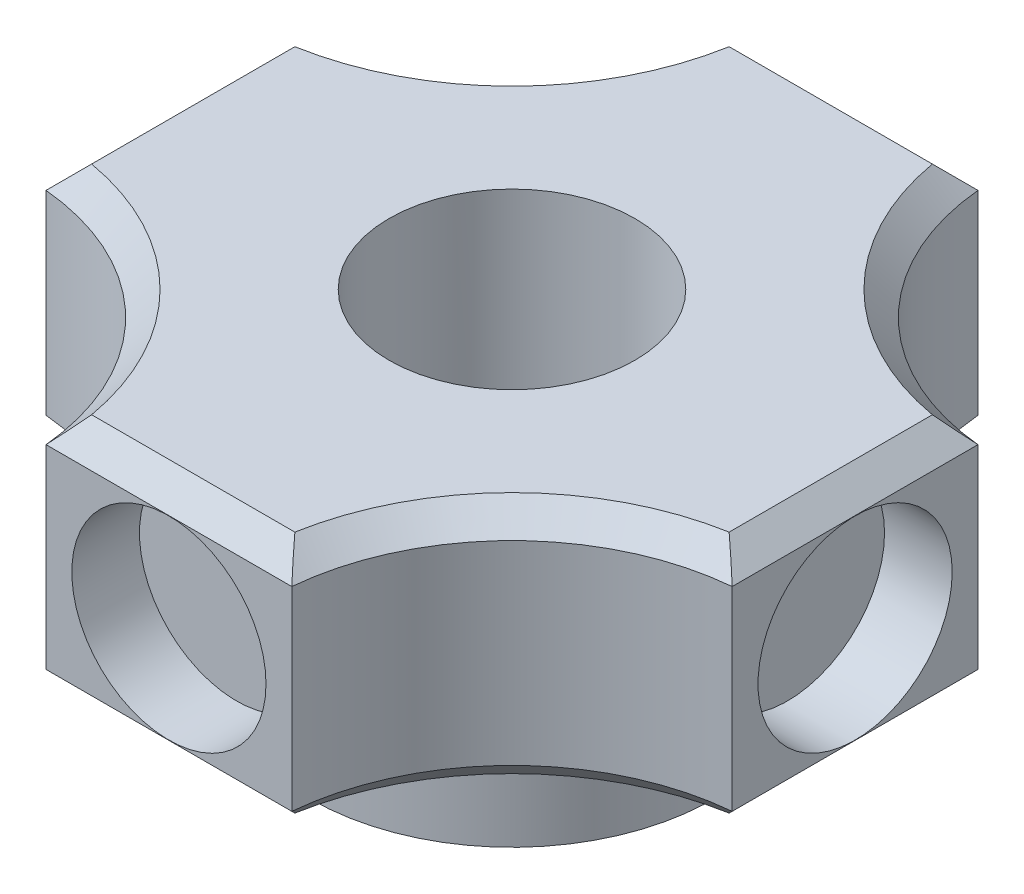
SolidWorks part; units mm, degrees
ref_plane "Front Plane" through (0, 0, 0) normal (0, 0, 1) x (1, 0, 0)
ref_plane "Top Plane" through (0, 0, 0) normal (0, 1, 0) x (1, 0, 0)
ref_plane "Right Plane" through (0, 0, 0) normal (1, 0, 0) x (0, 0, -1)
sketch "Sketch1" plane through (0, 0, 0) normal (0, 1, 0) x (1, 0, 0)
  line L2 (-5.05, 5.05) -> (-5.05, 14.0977)
  line L3 (-5.05, 14.0977) -> (5.05, 14.0977)
  line L4 (5.05, 5.05) -> (5.05, 14.0977)
  line L6 (-5.05, -5.05) -> (-5.05, -14.0977)
  line L7 (-5.05, -14.0977) -> (5.05, -14.0977)
  line L8 (5.05, -5.05) -> (5.05, -14.0977)
  line L9 (-5.05, -5.05) -> (-14.0977, -5.05)
  line L11 (-5.05, 5.05) -> (-14.0977, 5.05)
  line L12 (-14.0977, -5.05) -> (-14.0977, 5.05)
  line L13 (5.05, -5.05) -> (14.0977, -5.05)
  line L15 (5.05, 5.05) -> (14.0977, 5.05)
  line L16 (14.0977, -5.05) -> (14.0977, 5.05)
  circle A0 centre (0, 0) radius 5.05
  dimension "D1" = 10.1
  dimension "D2" = 5.05
extrude "Boss-Extrude1" add sketch "Sketch1" along normal blind 10
ref_axis "Axis1" through (0, 10, 0) along (0, -1, 0)
sketch "Sketch2" plane through (0, 0, 14.0977) normal (0, 0, 1) x (1, 0, 0)
  line L2 (-5.05, 10) -> (5.05, 10) construction
  line L3 (-5.05, 10) -> (-5.05, 0) construction
  circle A0 centre (0, 5) radius 3.99
  point P7 (0, 10)
  point P8 (-5.05, 5)
  dimension "D1" = 7.98
extrude "Cut-Extrude1" cut sketch "Sketch2" against normal blind 2.78 contours A0
pattern_circular "CirPattern1" count 4 every 90 about axis through (0, 10, 0) along (0, -1, 0) of "Cut-Extrude1"
fillet "Fillet1" radius 10 4 edges at (5.05, 5, 5.05) (-5.05, 5, 5.05) (-5.05, 5, -5.05) (5.05, 5, -5.05)
chamfer "Chamfer1" distance 1 angle 45 16 edges at (-14.0977, 0, 0) (-7.9374, 0, -7.9374) (0, 0, -14.0977) (7.9374, 0, -7.9374) (14.0977, 0, 0) (7.9374, 0, 7.9374) (0, 0, 14.0977) (-7.9374, 0, 7.9374) (-7.9374, 10, -7.9374) (0, 10, -14.0977) (7.9374, 10, -7.9374) (14.0977, 10, 0) (-7.9374, 10, 7.9374) (0, 10, 14.0977) (7.9374, 10, 7.9374) (-14.0977, 10, 0)
sketch "Sketch3" plane through (0, 0, 0) normal (0, -1, 0) x (1, 0, 0)
  circle A0 centre (0, 0) radius 8.2798
  circle A1 centre (0, 0) radius 5.05
extrude "Boss-Extrude2" add sketch "Sketch3" along normal blind 4
